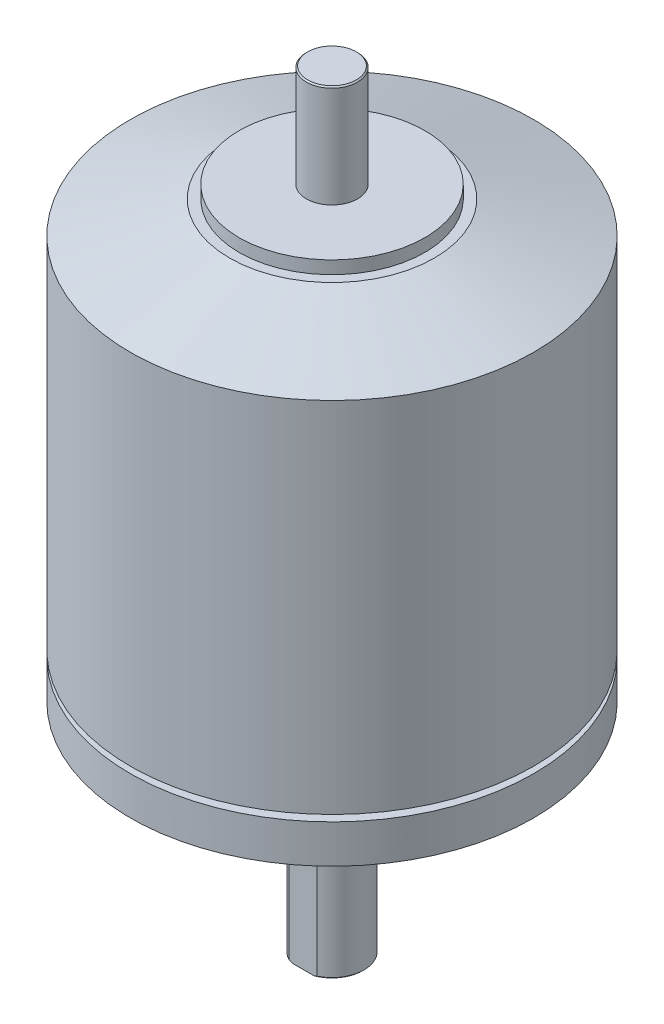
SolidWorks part; units mm, degrees
ref_plane "Front Plane" through (0, 0, 0) normal (0, 0, 1) x (1, 0, 0)
ref_plane "Top Plane" through (0, 0, 0) normal (0, 1, 0) x (1, 0, 0)
ref_plane "Right Plane" through (0, 0, 0) normal (1, 0, 0) x (0, 0, -1)
sketch "Sketch1" plane through (0, 0, 0) normal (0, 0, 1) x (1, 0, 0)
  line L0 (16, 72) -> (0, 72)
  line L1 (0, 72) -> (0, 0)
  line L2 (0, 0) -> (24, 0)
  line L3 (24, 0) -> (31.5, 4)
  line L4 (31.5, 4) -> (31.5, 10)
  line L5 (31.5, 10) -> (15, 10)
  line L6 (15, 10) -> (15, 11)
  line L7 (15, 11) -> (31.5, 11)
  line L8 (31.5, 11) -> (31.5, 67)
  line L9 (31.5, 67) -> (16, 72)
  line L10 (0, 72) -> (0, 0) construction
revolve "Revolve1" add sketch "Sketch1" angle 360 about L10 reverse direction yes
sketch "Sketch2" plane through (0, 72, 0) normal (0, 1, 0) x (-1, 0, 0)
  circle A0 centre (0, 0) radius 14.5
extrude "Boss-Extrude1" add sketch "Sketch2" along normal blind 2
sketch "Sketch3" plane through (0, 74, 0) normal (0, 1, 0) x (-1, 0, 0)
  circle A0 centre (0, 0) radius 4
extrude "Boss-Extrude2" add sketch "Sketch3" along normal blind 16
sketch "Sketch4" plane through (0, 0, 0) normal (0, -1, 0) x (1, 0, 0)
  circle A0 centre (0, 0) radius 5
extrude "Boss-Extrude3" add sketch "Sketch4" along normal blind 30
sketch "Sketch5" plane through (0, -30, 0) normal (0, -1, 0) x (1, 0, 0)
  line L0 (-2.1794, 4.5) -> (2.1794, 4.5)
  arc A0 (2.1794, 4.5) -> (-2.1794, 4.5) centre (0, 0) ccw
extrude "Cut-Extrude1" cut sketch "Sketch5" against normal blind 24
ref_plane "Plane1" through (-3.2, 0, 0) normal (1, 0, 0) x (0, 0, -1)
sketch "Sketch6" plane through (-3.2, 0, 0) normal (1, 0, 0) x (0, 0, -1)
  line L0 (1.5, -24.5) -> (1.5, -11.5)
  line L1 (-1.5, -11.5) -> (-1.5, -24.5)
  arc A0 (-1.5, -24.5) -> (1.5, -24.5) centre (0, -24.5) ccw
  arc A1 (1.5, -11.5) -> (-1.5, -11.5) centre (0, -11.5) ccw
sketch "Sketch15" plane through (0, 0, 0) normal (0, -1, 0) x (1, 0, 0)
  line L0 (0, 0) -> (-10.6066, 10.6066) construction
  line L1 (-10.6066, 10.6066) -> (-15.5563, 15.5563) construction
  line L2 (-30.3007, 0) -> (-10.0479, 0) construction
  circle A0 centre (-15.5563, 15.5563) radius 2
  circle A1 centre (-10.6066, 10.6066) radius 2
  circle A2 centre (15.5563, 15.5563) radius 2
  circle A3 centre (10.6066, 10.6066) radius 2
  circle A4 centre (15.5563, -15.5563) radius 2
  circle A5 centre (10.6066, -10.6066) radius 2
  circle A6 centre (-15.5563, -15.5563) radius 2
  circle A7 centre (-10.6066, -10.6066) radius 2
  point P7 (31.5, 27.0561)
  point P9 (0, 0)
  point P23 (0, 0)
  dimension "D1" = 4
  dimension "D2" = 7
  dimension "D3" = 15
  dimension "D4" = 45
  dimension "D5" = 4
extrude "Cut-Extrude3" cut sketch "Sketch15" against normal blind 10
extrude "Cut-Extrude4" cut sketch "Sketch6" against normal blind 10
chamfer "Chamfer1" distance 0.2 angle 45 2 edges at (0, 90, 4) (0, -30, -5)
